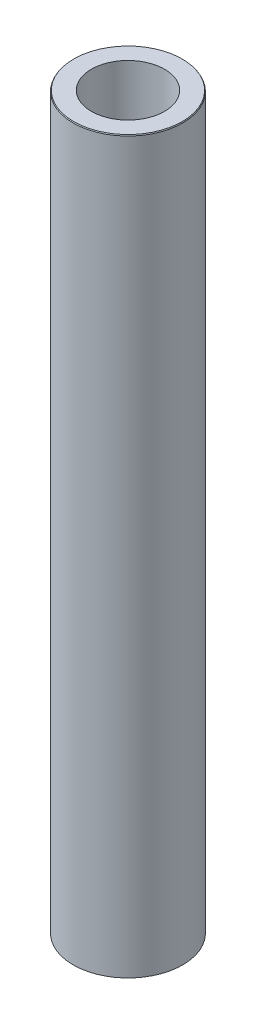
SolidWorks part; units mm, degrees
ref_plane "Front Plane" through (0, 0, 0) normal (0, 0, 1) x (1, 0, 0)
ref_plane "Top Plane" through (0, 0, 0) normal (0, 1, 0) x (1, 0, 0)
ref_plane "Right Plane" through (0, 0, 0) normal (1, 0, 0) x (0, 0, -1)
sketch "Sketch1" plane through (0, 0, 0) normal (0, 1, 0) x (1, 0, 0)
  circle A0 centre (0, 0) radius 45
  dimension "SHAFT_OD" = 90
extrude "Boss-Extrude1" add sketch "Sketch1" along normal blind 600
sketch "Sketch2" plane through (0, 0, 0) normal (0, 1, 0) x (1, 0, 0)
  circle A0 centre (0, 0) radius 30.0274
  dimension "BORE_D" = 60.0549
extrude "Cut-Extrude1" cut sketch "Sketch2" along normal through all
chamfer "Chamfer1" distance 0.7416 angle 31.743 2 edges at (0, 600, 45) (0, 0, 45) first distance on face at (0, 600, 45) first distance on face at (0, 0, 30.0274)
